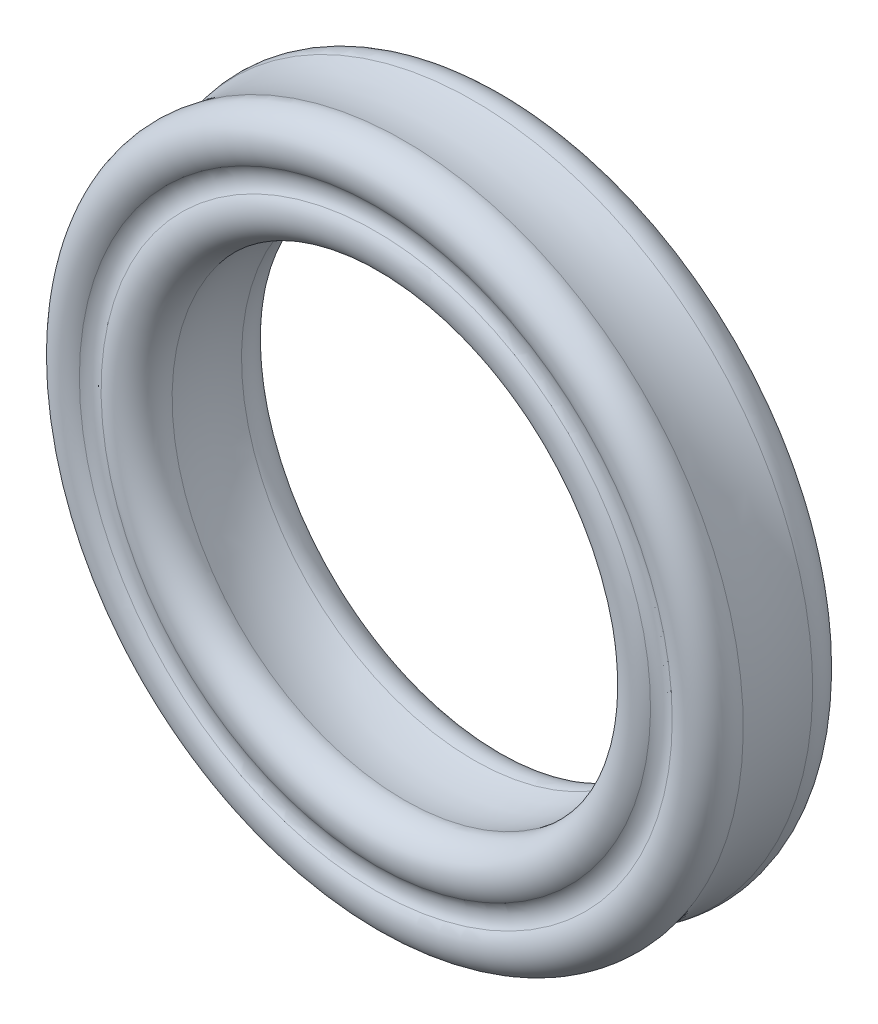
SolidWorks part; units mm, degrees
ref_plane "Plan1" through (0, 0, 0) normal (0, 0, 1) x (1, 0, 0)
ref_plane "Plan2" through (0, 0, 0) normal (0, 1, 0) x (1, 0, 0)
ref_plane "Plan3" through (0, 0, 0) normal (1, 0, 0) x (0, 0, -1)
sketch "Esquisse1" plane through (0, 0, 0) normal (1, 0, 0) x (0, 0, -1)
  line L0 (0, 0) -> (2, 0) construction
  line L1 (1, 4.95) -> (1, 3.37) construction
  line L2 (0, 4.95) -> (2, 4.95) construction
  line L3 (0, 4.95) -> (0, 3.37) construction
  line L4 (0, 3.37) -> (2, 3.37) construction
  line L5 (2, 4.95) -> (2, 3.37) construction
  line L6 (2, 4.16) -> (0, 4.16) construction
  arc A0 (0.4948, 4.9372) -> (0.079, 4.318) centre (0.395, 4.555) ccw
  arc A1 (0.4948, 3.3828) -> (0.079, 4.002) centre (0.395, 3.765) cw
  arc A2 (0.079, 4.002) -> (0.079, 4.318) centre (-0.1317, 4.16) ccw
  arc A3 (1.5052, 3.3828) -> (1.921, 4.002) centre (1.605, 3.765) ccw
  arc A4 (1.921, 4.002) -> (1.921, 4.318) centre (2.1317, 4.16) cw
  arc A5 (1.5052, 4.9372) -> (1.921, 4.318) centre (1.605, 4.555) cw
  arc A6 (0.4948, 4.9372) -> (1.5052, 4.9372) centre (1, 6.8723) ccw
  arc A7 (0.4948, 3.3828) -> (1.5052, 3.3828) centre (1, 1.4477) cw
  point P18 (0.395, 4.16)
  dimension "D4" = 0.79
  dimension "D5" = 0.2633
  dimension "D6" = 2
  dimension "E" = 1.58
  dimension "F" = 2
  dimension "De" = 4.95
revolve "Base-Révolution" add sketch "Esquisse1" angle 360 about L0
ref_axis "Axe1" through (0, 0, -50) along (0, 0, 1)
equation "\"D4@Esquisse1\"=\"E@Esquisse1\"/2"
equation "\"D5@Esquisse1\"=\"D4@Esquisse1\"/3"
equation "\"D6@Esquisse1\"=\"F@Esquisse1\""
